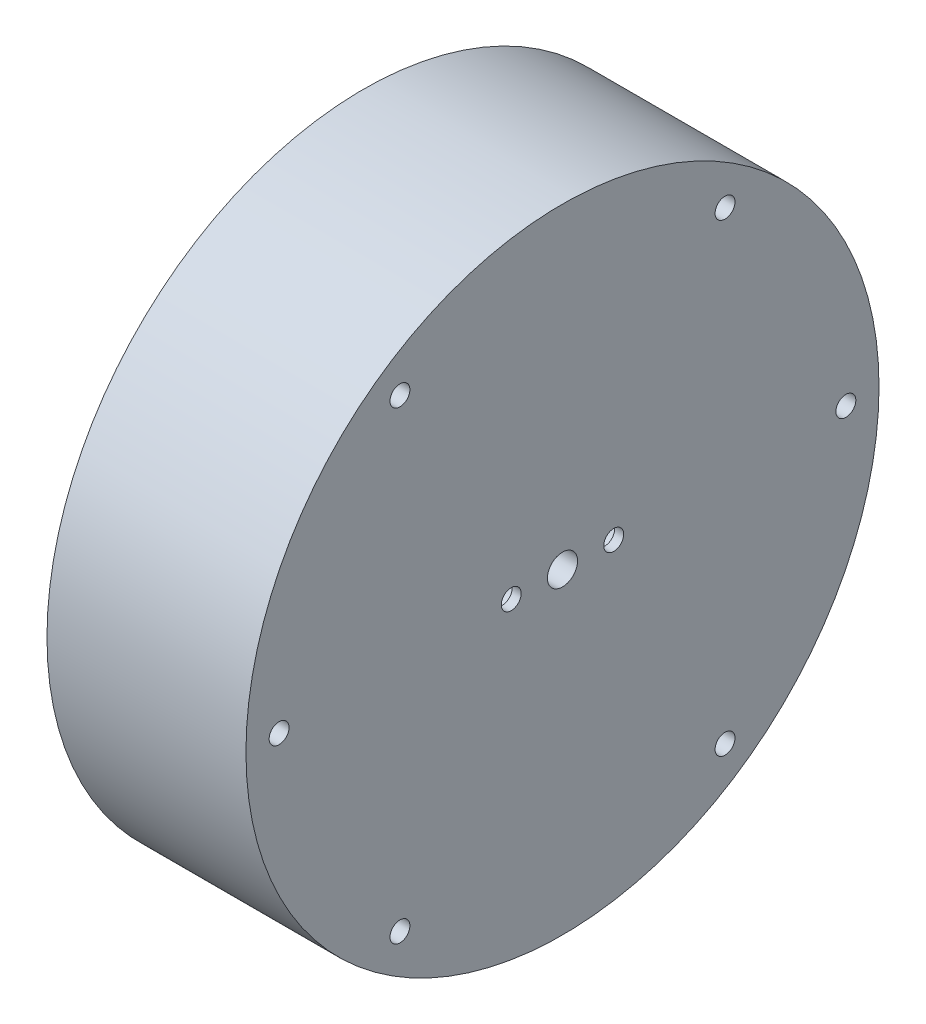
SolidWorks part; units mm, degrees
ref_plane "Plane1" through (0, 0, 0) normal (0, 0, 1) x (1, 0, 0)
ref_plane "Plane2" through (0, 0, 0) normal (0, 1, 0) x (1, 0, 0)
ref_plane "Plane3" through (0, 0, 0) normal (1, 0, 0) x (0, 0, -1)
sketch "HoldingSke" plane through (0, 0, 0) normal (0, 1, 0) x (1, 0, 0)
  line L0 (0, 0) -> (0.0872, -0.9962)
  line L1 (-15, 0) -> (100, 0) construction
  line L2 (0, 0) -> (-2.1039, 2.3779)
  line L3 (0, 0) -> (-11.863, 4.5341)
  line L4 (0, 0) -> (0.7527, 8.6031)
  line L5 (0, 0) -> (-23.7986, -8.8762)
  line L6 (0, 0) -> (-10.5278, -7.1032)
  line L7 (-2.1039, 2.3779) -> (3.3635, 27.1825)
  line L8 (-76.2, 3.3779) -> (-54.61, 3.3779)
  line L9 (-71.009, 38.7566) -> (-53.1078, 45.2721)
  line L10 (-76.2, 71.12) -> (104.1128, 71.12)
  line L11 (0, 0) -> (-15, 0)
  line L12 (-76.2, 101.6) -> (-76.162, 101.6)
  line L13 (24.9733, 27.94) -> (52.9518, 28.4284)
  line L14 (24.9733, 27.94) -> (24.9743, 27.94)
  line L15 (24.9733, 27.94) -> (100.4006, 29.5858)
  circle A0 centre (0, 0) radius 50
  circle A1 centre (0, 0) radius 12.7
  circle A2 centre (0, 0) radius 12.7
  dimension "MHD" = 25.4
  dimension "Hub_dia" = 25.4
  dimension "Diameter" = 100
  dimension "Num_teeth" = 85
  dimension "Pitch" = 1
  dimension "Overall_len" = 25.4
  dimension "Show_teeth" = 85
  dimension "Thickness" = 12.7
  dimension "OAL" = 25.4001
  dimension "T_dim" = 21.59
  dimension "Ap" = 20
  dimension "H" = 19.05
  dimension "Pitch_radius" = 180.3128
  dimension "Width" = 15
  dimension "Backlash" = 0.038
  dimension "Addendum_fac" = 1
  dimension "Dedendum_fac" = 1.25
  dimension "Clearance_fac" = 0.25
  dimension "Dedendum_add" = 0.001
  dimension "Module" = 1
sketch "BasProSke" plane through (0, 0, 0) normal (0, 1, 0) x (1, 0, 0)
  line L0 (-10, 0) -> (60, 0) construction
  line L1 (0, 41.5) -> (0, 50)
  line L2 (0, 41.5) -> (15, 41.5)
  line L3 (15, 41.5) -> (15, 50)
  line L4 (15, 50) -> (0, 50)
  dimension "Diameter" = 100
  dimension "Thickness" = 15
  dimension "Inside_diameter" = 83
revolve "Base-Revolve" add sketch "BasProSke" angle 360 about L0
sketch "TooCutSke" plane through (0, 0, 0) normal (1, 0, 0) x (0, 0, -1)
  line L3 (0.8804, 42.4909) -> (0.8804, 53.6633) construction
  line L4 (0, 0) -> (0, 59.563) construction
  line L5 (0, 0) -> (-2.5248, 68.2808) construction
  line L6 (-19.1021, 35.2615) -> (36.4888, 37.317) construction
  circle A0 centre (0, 0) radius 42.5 construction
  circle A1 centre (0, 0) radius 43.751 construction
  circle A2 centre (0, 0) radius 35.9432 construction
  circle A3 centre (0, 0) radius 41.4746 construction
  arc A4 (1.2248, 41.4565) -> (0.3791, 43.7494) centre (-19.1021, 35.2615) ccw
  arc A5 (1.2248, 41.4565) -> (-1.2248, 41.4565) centre (0, 0) ccw
  arc A6 (0.3791, 43.7494) -> (-0.3791, 43.7494) centre (0, 0) ccw
  arc A7 (-0.3791, 43.7494) -> (-1.2248, 41.4565) centre (19.1021, 35.2615) ccw
  dimension "Pitch_dia" = 85
  dimension "Base_dia" = 71.8865
  dimension "Root_dia" = 87.502
  dimension "Overcut_dia" = 82.9492
  dimension "Flank_rad" = 21.25
  dimension "Half_ang" = 2.118
  dimension "Half_CT" = 0.8804
extrude "ToothCut" cut sketch "TooCutSke" along normal through all
fillet "Breaks" [suppressed] radius 0.1
fillet "RootFillets" [suppressed] radius 0.251
pattern_circular "TeethCuts" count 85 every 4.235 about axis through (-10, 0, 0) along (1, 0, 0) of "RootFillets", "Breaks", "ToothCut"
sketch "Sketch1" plane through (15, 0, 0) normal (1, 0, 0) x (0, 0, -1)
  circle A0 centre (0, 0) radius 52.5
  dimension "D1" = 105
extrude "Boss-Extrude1" add sketch "Sketch1" along normal blind 4
sketch "Sketch2" plane through (19, 0, 0) normal (1, 0, 0) x (0, 0, -1)
  circle A0 centre (0, 0) radius 2.5
  dimension "D1" = 5
extrude "Cut-Extrude1" cut sketch "Sketch2" against normal blind 4
sketch "Sketch3" plane through (19, 0, 0) normal (1, 0, 0) x (0, 0, -1)
  line L0 (0, 0) -> (-8.5, 0) construction
  line L1 (0, 0) -> (8.5, 0) construction
  circle A0 centre (-8.5, 0) radius 1.65
  circle A1 centre (8.5, 0) radius 1.65
  dimension "D2" = 3.3
  dimension "D1" = 8.5
extrude "Cut-Extrude2" cut sketch "Sketch3" against normal blind 4
sketch "Sketch4" plane through (15, 0, 0) normal (-1, 0, 0) x (0, 0, 1)
  circle A0 centre (-8.5, 0) radius 2.75
  circle A1 centre (8.5, 0) radius 2.75
  dimension "D1" = 5.5
extrude "Cut-Extrude3" cut sketch "Sketch4" against normal blind 2.5
sketch "Sketch6" plane through (0, 0, 0) normal (-1, 0, 0) x (0, 0, 1)
  circle A0 centre (0, 0) radius 50
  circle A2 centre (0, 0) radius 39.55
extrude "Boss-Extrude3" add sketch "Sketch6" along normal blind 4
sketch "Sketch7" plane through (-4, 0, 0) normal (-1, 0, 0) x (0, 0, 1)
  circle A0 centre (0, 0) radius 50
  circle A1 centre (0, 0) radius 42.5
  dimension "D1" = 7.5
  dimension "D2" = 85
  dimension "D3" = 100
extrude "Boss-Extrude4" add sketch "Sketch7" along normal blind 10
sketch "Sketch8" plane through (-14, 0, 0) normal (-1, 0, 0) x (0, 0, 1)
  line L0 (0, 0) -> (-47, 0) construction
  line L1 (0, 0) -> (-47, 0) construction
  line L2 (0, 0) -> (-26.9581, 38.5001) construction
  line L3 (0, 0) -> (-26.9581, -38.5001) construction
  line L4 (0, 0) -> (47, 0) construction
  line L5 (0, 0) -> (26.9581, -38.5001) construction
  line L6 (0, 0) -> (26.9581, 38.5001) construction
  line L7 (-47, 0) -> (47, 0) construction
  circle A1 centre (-47, 0) radius 1.65
  circle A2 centre (-26.9581, 38.5001) radius 1.65
  circle A3 centre (-26.9581, -38.5001) radius 1.65
  circle A4 centre (47, 0) radius 1.65
  circle A5 centre (26.9581, 38.5001) radius 1.65
  circle A6 centre (26.9581, -38.5001) radius 1.65
  dimension "D1" = 47
  dimension "D3" = 3.3
  dimension "D2" = 55
  dimension "D4" = 55
  dimension "D5" = 55
  dimension "D6" = 55
sketch "Sketch9" plane through (15, 0, 0) normal (-1, 0, 0) x (0, 0, 1)
  circle A0 centre (0, 0) radius 50
  circle A1 centre (0, 0) radius 52.5
extrude "Boss-Extrude5" add sketch "Sketch9" along normal up to surface (29 mm away) up to face at (-14, 0, 50)
extrude "Cut-Extrude4" cut sketch "Sketch8" against normal through all
equation "' \"Module@HoldingSke\" = 6.35"
equation "' \"Num_teeth@HoldingSke\" = 24"
equation "' \"Ap@HoldingSke\" =  14.5"
equation "' \"Ap@HoldingSke\" = 14.5"
equation "' \"Width@HoldingSke\" = 12"
equation "' \"Diameter@HoldingSke\" = 8 * 25.4"
equation "' \"Show_teeth@HoldingSke\" = 100"
equation "' \"Backlash@HoldingSke\" = 0.009 * 25.4"
equation "' \"Addendum_fac@HoldingSke\" = 1.0"
equation "' \"Dedendum_fac@HoldingSke\" = 1.25"
equation "' \"Dedendum_add@HoldingSke\" = 0.00005 * 25.4"
equation "' \"Clearance_fac@HoldingSke\" = 0.25"
equation "\"Pitch@HoldingSke\" = 1 / \"Module@HoldingSke\" "
equation "\"Overcut_dia@TooCutSke\" = (\"Num_teeth@HoldingSke\" - 2 * \"Addendum_fac@HoldingSke\") / \"Pitch@HoldingSke\" - 0.002 * 25.4"
equation "\"Pitch_dia@TooCutSke\" = \"Num_teeth@HoldingSke\" / \"Pitch@HoldingSke\""
equation "\"Base_dia@TooCutSke\" = \"Num_teeth@HoldingSke\" / \"Pitch@HoldingSke\" * cos((\"Ap@HoldingSke\"  * 3.14159265 / 180)) * 0.90"
equation "\"Root_dia@TooCutSke\" = \"Num_teeth@HoldingSke\"  / \"Pitch@HoldingSke\" + 2 *  \"Dedendum_fac@HoldingSke\"/ \"Pitch@HoldingSke\" + \"Dedendum_add@HoldingSke\" * 2"
equation "\"Half_ang@TooCutSke\" = 180 / \"Num_teeth@HoldingSke\""
equation "\"Half_CT@TooCutSke\" = \"Num_teeth@HoldingSke\" / \"Pitch@HoldingSke\" * sin((3.14159265 / 2 / \"Num_teeth@HoldingSke\")) / 2 + 10 * \"Backlash@HoldingSke\" / 4"
equation "\"Flank_rad@TooCutSke\" = \"Num_teeth@HoldingSke\" / \"Pitch@HoldingSke\" / 4"
equation "\"Radius@RootFillets\"= \"Clearance_fac@HoldingSke\" / \"Pitch@HoldingSke\" + \"Dedendum_add@HoldingSke\""
equation "\"Break_rad@Breaks\" = 0.02 / \"Pitch@HoldingSke\" * 5"
equation "\"Num_teeth@TeethCuts\" = int( \"Show_teeth@HoldingSke\" ) + 1"
equation "\"Num_teeth@TeethCuts\" = ((sgn( \"Num_teeth@TeethCuts\" - \"Num_teeth@HoldingSke\" )-1)*( \"Num_teeth@TeethCuts\" - \"Num_teeth@HoldingSke\" ))/-2+ \"Num_teeth@HoldingSke\""
equation "\"Num_teeth@TeethCuts\" = ((sgn( \"Num_teeth@TeethCuts\" - 2.0)+1)*( \"Num_teeth@TeethCuts\" - 2.0))/2 +2.0"
equation "\"Angle@TeethCuts\" = 360.0 / \"Num_teeth@HoldingSke\""
equation "\"Diameter@BasProSke\" = \"Num_teeth@HoldingSke\"  / \"Pitch@HoldingSke\" + 2 *  \"Dedendum_fac@HoldingSke\"/ \"Pitch@HoldingSke\" + \"Dedendum_add@HoldingSke\" * 2 + 0.002 * 25.4"
equation "\"Diameter@BasProSke\" = ((sgn( \"Diameter@BasProSke\"  - \"Diameter@HoldingSke\" )+1)*( \"Diameter@BasProSke\"  - \"Diameter@HoldingSke\" ))/2 + \"Diameter@HoldingSke\""
equation "\"Inside_diameter@BasProSke\" =  (\"Num_teeth@HoldingSke\" - 2 * \"Addendum_fac@HoldingSke\") / \"Pitch@HoldingSke\" "
equation "\"Thickness@BasProSke\"  = \"Width@HoldingSke\""
